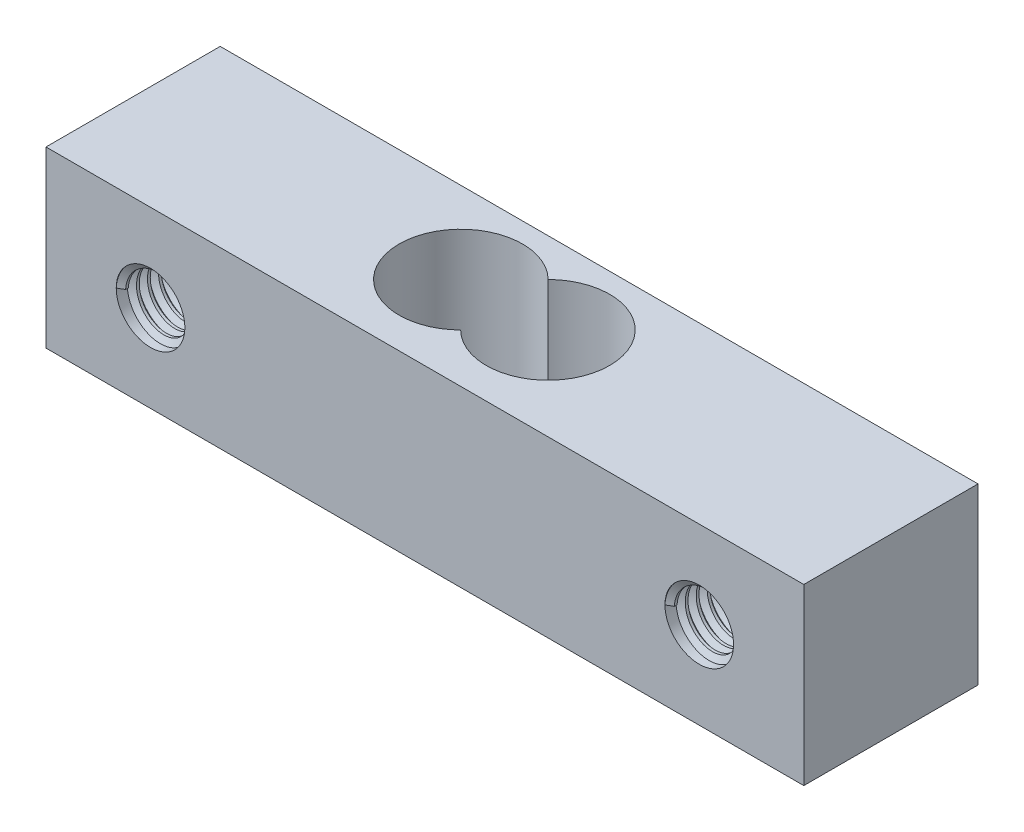
SolidWorks part; units mm, degrees
material "1060 Alloy"
ref_plane "Front Plane" through (0, 0, 0) normal (0, 0, 1) x (1, 0, 0)
ref_plane "Top Plane" through (0, 0, 0) normal (0, 1, 0) x (1, 0, 0)
ref_plane "Right Plane" through (0, 0, 0) normal (1, 0, 0) x (0, 0, -1)
sketch "Sketch1" plane through (0, 0, 0) normal (0, 0, 1) x (1, 0, 0)
  line L0 (0, 0) -> (55.245, 0)
  line L1 (55.245, 0) -> (55.245, 12.7)
  line L2 (55.245, 12.7) -> (0, 12.7)
  line L3 (0, 12.7) -> (0, 0)
  dimension "D1" = 55.245
  dimension "D2" = 12.7
extrude "Boss-Extrude1" add sketch "Sketch1" along normal blind 12.7
hole_wizard "Ø5.0mm Dowel Hole1" positions "Sketch2" profile "Sketch3" hole size "Ø5.0" standard "ANSI Metric" end condition through all
sketch "Sketch2" plane through (0, 0, 12.7) normal (0, 0, 1) x (1, 0, 0)
  line L0 (0, 12.7) -> (0, 0) construction
  line L1 (0, 0) -> (55.245, 0) construction
  point P0 (7.62, 6.35)
  point P2 (47.625, 6.35)
  dimension "D1" = 40.005
  dimension "D2" = 7.62
  dimension "D3" = 6.35
sketch "Sketch3" plane through (7.62, 6.35, 12.7) normal (1, 0, 0) x (0, -1, 0)
  line L0 (0, 0) -> (0, 12.7)
  line L1 (0, 12.7) -> (2.5, 12.7)
  line L2 (2.5, 12.7) -> (2.5, 0)
  line L5 (2.5, 0) -> (0, 0)
  line L11 (0, -6.35) -> (0, 107.95) construction
  dimension "Thru Hole Dia." = 5
  dimension "Thru Hole Depth" = 12.7
thread "Thread1" pitch 0.8 method extrude profile "Thread Profile2" start angle 0, offset 0, length 12.0652, pitch 0.8, diameter 5
ref_plane "Plane2" through (5.12, 6.35, 12.7) normal (0, -1, 0) x (-1, 0, 0)
sketch "Thread Profile2" plane through (5.12, 6.35, 12.7) normal (0, -1, 0) x (-1, 0, 0)
  line L0 (0, 0) -> (0, 0.8) construction
  line L11 (0, 0) -> (0, 0.7)
  line L12 (0, 0.7) -> (-0.433, 0.45)
  line L13 (-0.433, 0.45) -> (-0.433, 0.25)
  line L15 (-0.433, 0.25) -> (0, 0)
  line L17 (-0.433, 0.35) -> (0, 0.35) construction
  point P2 (0, 0)
  dimension "Pitch" = 0.8
  dimension "Profile_Angle" = 60
  dimension "Profile_Land" = 0.2
  dimension "Profile_Height" = 0.433
thread "Thread2" pitch 0.8 method extrude profile "Thread Profile3" start angle 0, offset 0, length 12.065, pitch 0.8, diameter 5
ref_plane "Plane3" through (45.125, 6.35, 12.7) normal (0, -1, 0) x (-1, 0, 0)
sketch "Thread Profile3" plane through (45.125, 6.35, 12.7) normal (0, -1, 0) x (-1, 0, 0)
  line L0 (0, 0) -> (0, 0.8) construction
  line L11 (0, 0) -> (0, 0.7)
  line L12 (0, 0.7) -> (-0.433, 0.45)
  line L13 (-0.433, 0.45) -> (-0.433, 0.25)
  line L15 (-0.433, 0.25) -> (0, 0)
  line L17 (-0.433, 0.35) -> (0, 0.35) construction
  point P2 (0, 0)
  dimension "Pitch" = 0.8
  dimension "Profile_Angle" = 60
  dimension "Profile_Land" = 0.2
  dimension "Profile_Height" = 0.433
hole_wizard "Ø8.0mm Dowel Hole2" positions "Sketch24" profile "Sketch25" hole size "Ø8.0" standard "ANSI Metric" end condition through all
sketch "Sketch24" plane through (0, 12.7, 0) normal (0, 1, 0) x (1, 0, 0)
  line L0 (0, -12.7) -> (0, 0) construction
  point P0 (23.495, -5.953)
  point P2 (29.845, -5.953)
  dimension "D1" = 6.35
  dimension "D2" = 23.495
sketch "Sketch25" plane through (23.495, 12.7, 5.953) normal (1, 0, 0) x (0, 0, 1)
  line L0 (0, 0) -> (0, 12.7)
  line L1 (0, 12.7) -> (4.5, 12.7)
  line L2 (4.5, 12.7) -> (4.5, 0)
  line L5 (4.5, 0) -> (0, 0)
  line L11 (0, -6.35) -> (0, 107.95) construction
  dimension "Thru Hole Dia." = 9
  dimension "Thru Hole Depth" = 12.7
